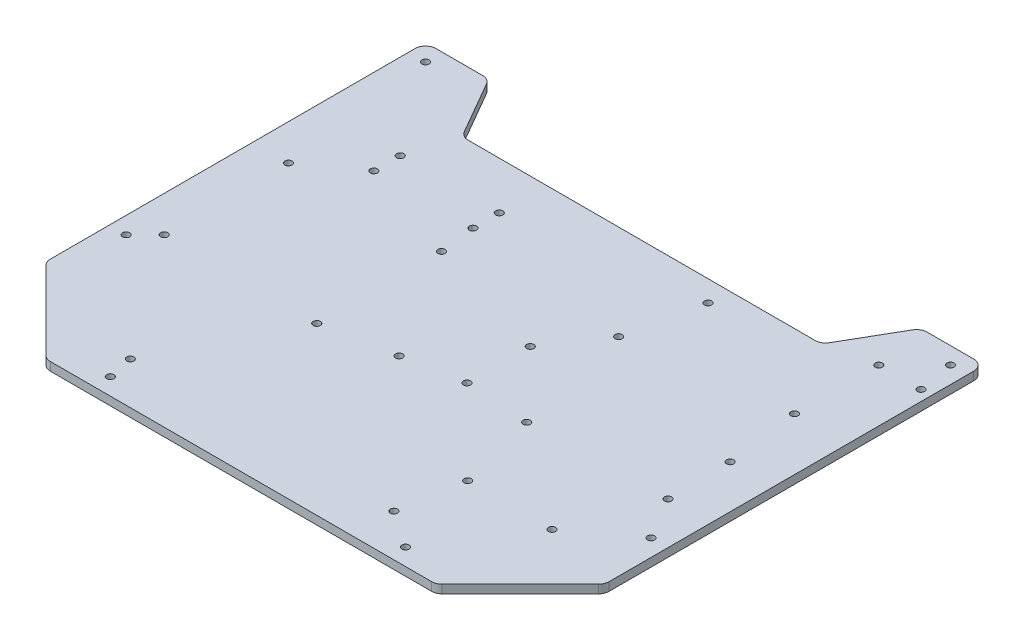
SolidWorks part; units mm, degrees
material "Acier non allié"
ref_plane "Front" through (0, 0, 0) normal (0, 0, 1) x (1, 0, 0)
ref_plane "Top" through (0, 0, 0) normal (0, 1, 0) x (1, 0, 0)
ref_plane "Right" through (0, 0, 0) normal (1, 0, 0) x (0, 0, -1)
sketch "Main scetch" plane through (0, 0, 0) normal (0, 1, 0) x (1, 0, 0)
  line L1 (0, 0) -> (132.5, 0) construction
  line L2 (0, 0) -> (0, 220) construction
  line L3 (0, 220) -> (132.5, 220) construction
  line L4 (132.5, 0) -> (132.5, 220) construction
  line L13 (-92.5, 0) -> (92.5, 0)
  line L14 (92.5, 0) -> (132.5, 40)
  line L15 (132.5, 40) -> (132.5, 220)
  line L16 (132.5, 220) -> (102.5, 220)
  line L17 (102.5, 220) -> (85.1795, 190)
  line L18 (85.1795, 190) -> (-85.1795, 190)
  line L19 (-102.5, 220) -> (-85.1795, 190)
  line L20 (-132.5, 220) -> (-102.5, 220)
  line L21 (-132.5, 40) -> (-132.5, 220)
  line L22 (-92.5, 0) -> (-132.5, 40)
  point P11 (0, 190)
  dimension "132.5" = 132.5
  dimension "D2" = 220
  dimension "D1" = 40
  dimension "D3" = 40
  dimension "D4" = 30
  dimension "D5" = 60
  dimension "D6" = 30
extrude "Main extrusion" add sketch "Main scetch" along normal blind 4
fillet "Congé1" radius 5 10 edges at (-132.5, 2, -40) (-92.5, 2, 0) (92.5, 2, 0) (132.5, 2, -40) (132.5, 2, -220) (102.5, 2, -220) (85.1795, 2, -190) (-85.1795, 2, -190) (-102.5, 2, -220) (-132.5, 2, -220)
sketch "Esquisse1" plane through (0, 4, 0) normal (0, 1, 0) x (1, 0, 0)
  line L0 (0, 0) -> (0, 218.5516) construction
  line L1 (132.5, 42.0711) -> (132.5, 215) construction
  line L2 (127.5, 220) -> (105.3868, 220) construction
  line L3 (-90.4289, 0) -> (90.4289, 0) construction
  circle A0 centre (70, 8) radius 1
  circle A1 centre (124.5, 70) radius 1
  circle A2 centre (124.5, 212) radius 1
  circle A3 centre (-124.5, 212) radius 1
  circle A4 centre (-124.5, 70) radius 1
  circle A5 centre (-70, 8) radius 1
  dimension "D1" = 2
  dimension "D2" = 2
  dimension "D3" = 2
  dimension "D4" = 8
  dimension "D5" = 8
  dimension "D6" = 8
  dimension "D7" = 8
  dimension "D8" = 70
  dimension "D9" = 70
extrude "Enlèv. mat.-Extru.1" cut sketch "Esquisse1" against normal through all
hole_wizard "Dégagement M31" positions "Esquisse2" profile "Esquisse3" hole size "M3" standard "ISO" end condition through all
sketch "Esquisse2" plane through (0, 4, 0) normal (0, 1, 0) x (1, 0, 0)
  point P0 (-124.5, 212)
  point P3 (-124.5, 70)
  point P6 (-70, 8)
  point P9 (70, 8)
  point P12 (124.5, 70)
  point P15 (124.5, 212)
sketch "Esquisse3" plane through (-124.5, 4, -212) normal (1, 0, 0) x (0, 0, 1)
  line L0 (0, 0) -> (0, 4)
  line L1 (0, 4) -> (1.7, 4)
  line L2 (1.7, 4) -> (1.7, 0)
  line L5 (1.7, 0) -> (0, 0)
  line L11 (0, -6.35) -> (0, 107.95) construction
  dimension "Diamètre du perçage jusqu'au prochain" = 3.4
  dimension "Profondeur du perçage jusqu'au prochain" = 4
sketch "Esquisse4" plane through (0, 4, 0) normal (0, 1, 0) x (1, 0, 0)
  line L0 (-132.5, 215) -> (-132.5, 42.0711) construction
  line L2 (82.2927, 190) -> (-82.2927, 190) construction
  line L3 (132.5, 42.0711) -> (132.5, 215) construction
  line L4 (-90.4289, 0) -> (90.4289, 0) construction
  line L5 (127.5, 220) -> (105.3868, 220) construction
  circle A1 centre (-68.5, 185) radius 1 construction
  circle A5 centre (41.5, 180) radius 1
  circle A6 centre (34.12, 145) radius 1
  circle A7 centre (107.5, 155) radius 1
  circle A8 centre (127.5, 195) radius 1
  circle A9 centre (112, 120) radius 1
  circle A10 centre (112.5, 90) radius 1
  circle A11 centre (17.2, 120) radius 1
  circle A12 centre (17.2, 90) radius 1
  circle A13 centre (47.5, 88) radius 1
  circle A14 centre (57.5, 50) radius 1
  circle A15 centre (97.5, 50) radius 1
  circle A16 centre (52.5, 20) radius 1
  circle A17 centre (-10, 85) radius 1
  circle A18 centre (-72.5, 20) radius 1
  circle A19 centre (107.5, 195) radius 1
  circle A23 centre (-115.5, 138) radius 1
  circle A24 centre (-42.86, 138) radius 1
  circle A25 centre (-115.5, 79.07) radius 1
  circle A26 centre (-42.8904, 78.82) radius 1
  circle A27 centre (-92, 167.5) radius 1
  circle A28 centre (-45, 167.5) radius 1
  circle A29 centre (-92, 155) radius 1
  circle A30 centre (-45, 155) radius 1
  point P58 (0, 0)
  dimension "D4" = 2
  dimension "D13" = 2
  dimension "D16" = 2
  dimension "D19" = 2
  dimension "D24" = 2
  dimension "D25" = 2
  dimension "D28" = 2
  dimension "D30" = 2
  dimension "D32" = 2
  dimension "D36" = 2
  dimension "D37" = 2
  dimension "D40" = 2
  dimension "D48" = 2
  dimension "D49" = 2
  dimension "D50" = 2
  dimension "D52" = 2
  dimension "D11" = 2
  dimension "D12" = 2
  dimension "D65" = 2
  dimension "D66" = 2
  dimension "D58" = 2
  dimension "D61" = 2
  dimension "D70" = 2
  dimension "D71" = 2
  dimension "D14" = 174
  dimension "D15" = 10
  dimension "D17" = 166.62
  dimension "D18" = 45
  dimension "D20" = 25
  dimension "D21" = 65
  dimension "D22" = 5
  dimension "D23" = 25
  dimension "D26" = 20.5
  dimension "D27" = 100
  dimension "D29" = 30
  dimension "D31" = 115.3
  dimension "D33" = 115.3
  dimension "D34" = 132
  dimension "D35" = 85
  dimension "D38" = 50
  dimension "D39" = 75
  dimension "D41" = 35
  dimension "D42" = 80
  dimension "D43" = 20
  dimension "D44" = 20
  dimension "D45" = 205
  dimension "D46" = 85
  dimension "D47" = 142.5
  dimension "D51" = 25
  dimension "D53" = 25
  dimension "D54" = 5
  dimension "D55" = 64
  dimension "D7" = 59.18
  dimension "D8" = 72.64
  dimension "D9" = 58.93
  dimension "D10" = 72.61
  dimension "D67" = 17
  dimension "D68" = 138
  dimension "D56" = 23.5
  dimension "D57" = 23.5
  dimension "D59" = 17.5
  dimension "D60" = 17.5
  dimension "D62" = 12.5
  dimension "D63" = 12.5
  dimension "D64" = 23.5
  dimension "D69" = 23.5
extrude "Enlèv. mat.-Extru.2" cut sketch "Esquisse4" against normal through all
hole_wizard "Dégagement M32" positions "Esquisse5" profile "Esquisse6" hole size "M3" standard "ISO" end condition through all
sketch "Esquisse5" plane through (0, 4, 0) normal (0, 1, 0) x (1, 0, 0)
  point P9 (17.2, 120)
  point P18 (34.12, 145)
  point P21 (41.5, 180)
  point P24 (107.5, 155)
  point P27 (127.5, 195)
  point P30 (112, 120)
  point P33 (112.5, 90)
  point P36 (47.5, 88)
  point P39 (17.2, 90)
  point P42 (57.5, 50)
  point P45 (97.5, 50)
  point P48 (-10, 85)
  point P51 (-72.5, 20)
  point P54 (52.5, 20)
  point P57 (107.5, 195)
  point P86 (-115.5, 138)
  point P89 (-42.86, 138)
  point P92 (-115.5, 79.07)
  point P95 (-42.8904, 78.82)
  point P102 (-92, 167.5)
  point P105 (-92, 155)
  point P108 (-45, 155)
  point P111 (-45, 167.5)
  point P115 (0, 0)
sketch "Esquisse6" plane through (17.2, 4, -120) normal (1, 0, 0) x (0, 0, 1)
  line L0 (0, 0) -> (0, 4)
  line L1 (0, 4) -> (1.7, 4)
  line L2 (1.7, 4) -> (1.7, 0)
  line L5 (1.7, 0) -> (0, 0)
  line L11 (0, -6.35) -> (0, 107.95) construction
  dimension "Diamètre du perçage jusqu'au prochain" = 3.4
  dimension "Profondeur du perçage jusqu'au prochain" = 4
equation "\"WIDTH\"= 300mm'Total width of the robot"
equation "\"LENGTH\"= 220mm'Total length of the robot"
equation "\"D2@Main scetch\" = \"LENGTH\""
equation "\"CUT_DEPTH\"= 45mm'Depth of the cut on the edges of the plate"
equation "\"Plate_th\"= 3mm'Thickness of the plate"
equation "\"D1\"= \"Plate_th\""
equation "\"D47@Esquisse4\"=(80+205)/2"
